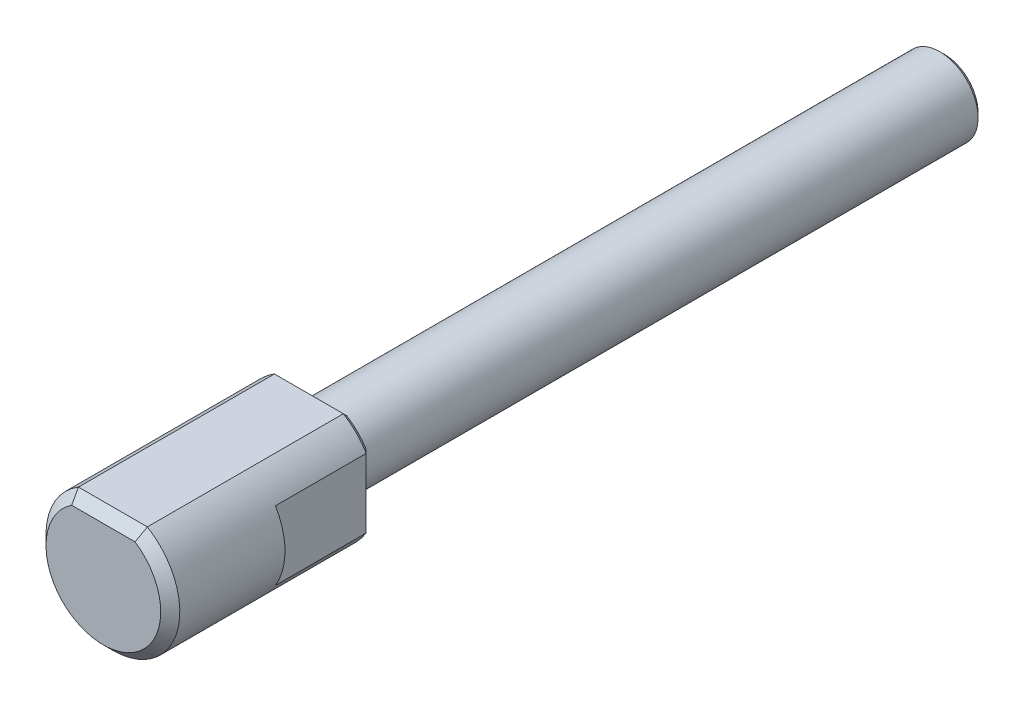
SolidWorks part; units mm, degrees
ref_plane "Front Plane" through (0, 0, 0) normal (0, 0, 1) x (1, 0, 0)
ref_plane "Top Plane" through (0, 0, 0) normal (0, 1, 0) x (1, 0, 0)
ref_plane "Right Plane" through (0, 0, 0) normal (1, 0, 0) x (0, 0, -1)
ref_plane "Plane1" through (0, 0, 88) normal (0, 0, 1) x (1, 0, 0)
sketch "Sketch1" plane through (0, 0, 88) normal (0, 0, 1) x (1, 0, 0)
  line L0 (3.6056, 6) -> (-3.6056, 6)
  arc A0 (-3.6056, 6) -> (3.6056, 6) centre (0, 0) ccw
extrude "Boss-Extrude1" add sketch "Sketch1" against normal blind 12
sketch "Sketch2" plane through (0, 0, 76) normal (0, 0, -1) x (-1, 0, 0)
  line L1 (-6, -3.6056) -> (-6, 3.6056)
  line L2 (-3.6056, 6) -> (3.6056, 6)
  line L4 (6, 3.6056) -> (6, -3.6056)
  line L5 (3.6056, -6) -> (-3.6056, -6)
  arc A0 (-6, -3.6056) -> (-3.6056, -6) centre (0, 0) ccw
  arc A1 (-3.6056, 6) -> (-6, 3.6056) centre (0, 0) ccw
  arc A2 (6, 3.6056) -> (3.6056, 6) centre (0, 0) ccw
  arc A3 (3.6056, -6) -> (6, -3.6056) centre (0, 0) ccw
extrude "Boss-Extrude2" add sketch "Sketch2" along normal blind 10
ref_plane "Plane2" through (0, 0, 0) normal (0, -1, 0) x (1, 0, 0)
sketch "Sketch3" plane through (0, 0, 0) normal (0, -1, 0) x (1, 0, 0)
  line L0 (4, 66) -> (0, 66)
  line L1 (0, 66) -> (0, 0)
  line L2 (0, 0) -> (4, 0)
  line L3 (4, 0) -> (4, 66)
  line L4 (0, 66) -> (0, 0) construction
revolve "Revolve1" add sketch "Sketch3" angle 360 about L4 reverse direction yes
chamfer "Chamfer3" distance 1 angle 45 2 edges at (0, -7, 88) (0, 6, 88)
chamfer "Chamfer4" distance 0.5 angle 45 8 edges at (-4.9497, -4.9497, 66) (-6, 0, 66) (-4.9497, 4.9497, 66) (0, -6, 66) (4.9497, -4.9497, 66) (6, 0, 66) (4.9497, 4.9497, 66) (0, 6, 66)
chamfer "Chamfer5" distance 0.5 angle 45 1 edges at (-4, 0, 0)
